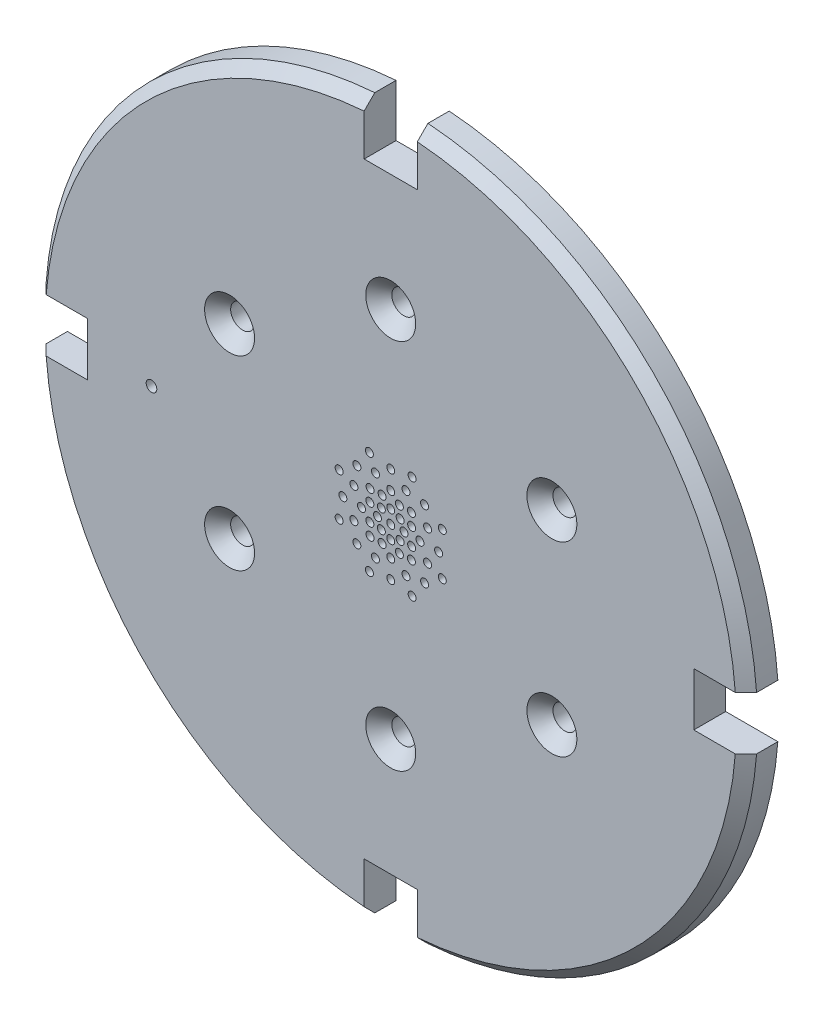
SolidWorks part; units mm, degrees
material "7075-T6 (SN)"
ref_plane "Płaszczyzna przednia" through (0, 0, 0) normal (0, 0, 1) x (1, 0, 0)
ref_plane "Płaszczyzna górna" through (0, 0, 0) normal (0, 1, 0) x (1, 0, 0)
ref_plane "Płaszczyzna prawa" through (0, 0, 0) normal (1, 0, 0) x (0, 0, -1)
sketch "Szkic1" plane through (0, 0, 0) normal (0, 0, 1) x (1, 0, 0)
  circle A0 centre (0, 0) radius 67
  dimension "D1" = 134
extrude "Dodanie-wyciągnięcie1" add sketch "Szkic1" along normal blind 6
chamfer "Sfazowanie1" distance 2 1 edges at (67, 0, 6)
sketch "Szkic2" plane through (0, 0, 6) normal (0, 0, 1) x (1, 0, 0)
  line L0 (0, 12.06) -> (0, 0) construction
  line L1 (0, 0) -> (4.6152, 11.142) construction
  circle A1 centre (0, 0) radius 12.06
  circle A3 centre (0, 0) radius 4.25 construction
  circle A4 centre (0, 0) radius 5.5 construction
  circle A5 centre (0, 0) radius 9 construction
  circle A7 centre (0, 0) radius 7.5 construction
  circle A8 centre (0, 0) radius 10.5 construction
  circle A9 centre (0, 0) radius 24.12 construction
  circle A11 centre (0, 0) radius 2.5 construction
  point P12 (0, 2.5)
  point P13 (0, 0)
  point P14 (0, 0)
  point P16 (0, 5.5)
  point P18 (0, 9)
  point P20 (1.6264, 3.9265)
  point P21 (2.8701, 6.9291)
  point P22 (4.0182, 9.7007)
  dimension "D1" = 24.12
  dimension "D2" = 22.5
  dimension "D3" = 8.5
  dimension "D4" = 11
  dimension "D5" = 18
  dimension "D6" = 21
  dimension "D7" = 15
  dimension "D8" = 48.24
  dimension "D9" = 5
ref_axis "Oś1" through (0, 0, 12.2009) along (0, 0, -1)
hole_wizard "Otwory ustalające Ø1.5mm1" positions "Szkic3" profile "Szkic4" hole size "Ø1.5" standard "ISO"
sketch "Szkic3" plane through (0, 0, 6) normal (0, 0, 1) x (1, 0, 0)
  point P0 (0, 0)
sketch "Szkic4" plane through (0, 0, 6) normal (1, 0, 0) x (0, -1, 0)
  line L0 (0, 0) -> (0, 6.4506)
  line L1 (0, 6.4506) -> (0.75, 6)
  line L2 (0.75, 6) -> (0.75, 0)
  line L5 (0.75, 0) -> (0, 0)
  line L10 (0, 6.4506) -> (-0.75, 6) construction
  line L11 (0, -6.35) -> (0, 107.95) construction
  dimension "Średnica otworu" = 1.5
  dimension "Głębokość otworu" = 6
  dimension "Kąt wiertła" = 118
hole_wizard "Otwory ustalające Ø1.5mm2" positions "Szkic5" profile "Szkic6" hole size "Ø1.5" standard "ISO"
sketch "Szkic5" plane through (0, 0, 6) normal (0, 0, 1) x (1, 0, 0)
  point P0 (0, 2.5)
  point P3 (1.6264, 3.9265)
  point P6 (0, 5.5)
  point P9 (2.8701, 6.9291)
  point P12 (0, 9)
  point P15 (4.0182, 9.7007)
sketch "Szkic6" plane through (0, 2.5, 6) normal (1, 0, 0) x (0, -1, 0)
  line L0 (0, 0) -> (0, 6.4506)
  line L1 (0, 6.4506) -> (0.75, 6)
  line L2 (0.75, 6) -> (0.75, 0)
  line L5 (0.75, 0) -> (0, 0)
  line L10 (0, 6.4506) -> (-0.75, 6) construction
  line L11 (0, -6.35) -> (0, 107.95) construction
  dimension "Średnica otworu" = 1.5
  dimension "Głębokość otworu" = 6
  dimension "Kąt wiertła" = 118
pattern_circular "Szyk kołowy1" count 8 over 360 about axis through (0, 0, 12.2009) along (0, 0, -1) of "Otwory ustalające Ø1.5mm2"
sketch "Szkic7" plane through (0, 0, 6) normal (0, 0, 1) x (1, 0, 0)
  circle A0 centre (0, 0) radius 35 construction
  circle A1 centre (0, 35) radius 2.05
  dimension "D1" = 70
  dimension "D2" = 4.1
extrude "Wytnij-wyciągnięcie1" cut sketch "Szkic7" against normal up to next
pattern_circular "Szyk kołowy2" count 6 over 360 about axis through (0, 0, 12.2009) along (0, 0, -1) of "Wytnij-wyciągnięcie1"
ref_plane "Płaszczyzna2" through (0, 0, 6) normal (0, 0, 1) x (1, 0, 0)
sketch "Szkic8" plane through (0, 0, 6) normal (0, 0, 1) x (1, 0, 0)
  line L1 (-65, 0) -> (65, 0) construction
  circle A0 centre (0, 0) radius 65 construction
  circle A1 centre (-45, 0) radius 1
  dimension "D2" = 2
  dimension "D4" = 45
extrude "Wytnij-wyciągnięcie2" cut sketch "Szkic8" against normal mid plane 40 contours A1
sketch "Szkic9" plane through (0, 0, 6) normal (0, 0, 1) x (1, 0, 0)
  line L0 (-65, 0) -> (65, 0) construction
  line L1 (57, 5) -> (67, 5)
  line L2 (57, 5) -> (57, -5)
  line L3 (57, -5) -> (67, -5)
  line L4 (67, 5) -> (67, -5)
  circle A0 centre (0, 0) radius 67 construction
  point P4 (57, 0)
  dimension "D1" = 10
  dimension "D2" = 10
extrude "Wytnij-wyciągnięcie3" cut sketch "Szkic9" against normal blind 10
pattern_circular "Szyk kołowy3" count 4 over 360 about axis through (0, 0, 6) along (0, 0, 1) of "Wytnij-wyciągnięcie3"
hole_wizard "Pogłębienie stożkowe pod M4 wkręt do części metalowych z łbem soczewkowym1" positions "Szkic 3D5" profile "Szkic14" countersink size "M4" standard "Ansi Metric" end condition through all
sketch3d "Szkic 3D5"
  circle A0 centre (0, 35, 6) radius 2.05 construction
  point P0 (0, 35, 6)
  point P6 (0, 35, 8.05)
  dimension "D1" = 35.5106
sketch "Szkic14" plane through (0, 35, 6) normal (1, 0, 0) x (0, -1, 0)
  line L0 (0, 0) -> (0, 6)
  line L1 (0, 6) -> (2.25, 6)
  line L2 (2.25, 6) -> (2.25, 2.45)
  line L3 (2.25, 2.45) -> (4.7, 0)
  line L5 (4.7, 0) -> (0, 0)
  line L6 (-2.25, 2.45) -> (-4.7, 0) construction
  line L11 (0, -6.35) -> (0, 107.95) construction
  dimension "Średnica otworu na wylot" = 4.5
  dimension "Głębokość otworu na wylot" = 6
  dimension "Średnica zewnętrznego pogłębienia stożkowego" = 9.4
  dimension "Kąt zewnętrznego pogłębienia stożkowego" = 90
pattern_circular "Szyk kołowy4" count 6 over 360 about axis through (0, 0, 12.2009) along (0, 0, -1) of "Pogłębienie stożkowe pod M4 wkręt do części metalowych z łbem soczewkowym1"
